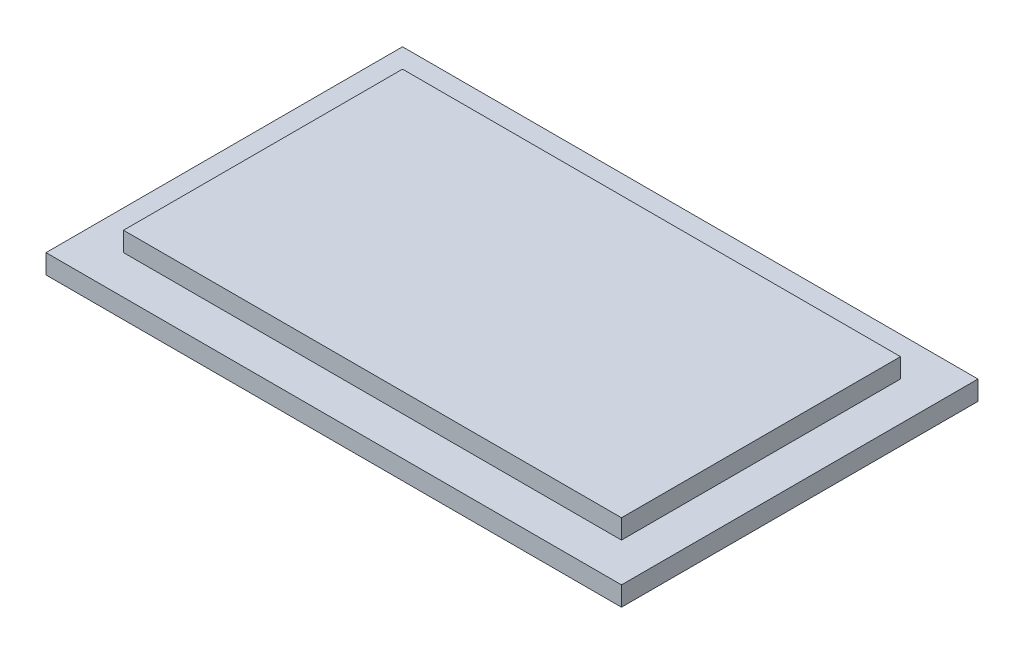
SolidWorks part; units mm, degrees
ref_plane "Front Plane" through (0, 0, 0) normal (0, 0, 1) x (1, 0, 0)
ref_plane "Top Plane" through (0, 0, 0) normal (0, 1, 0) x (1, 0, 0)
ref_plane "Right Plane" through (0, 0, 0) normal (1, 0, 0) x (0, 0, -1)
sketch "Sketch1" plane through (0, 0, 0) normal (0, 1, 0) x (1, 0, 0)
  line L0 (-18.4385, 2.948) -> (-18.4385, -15.452)
  line L1 (-18.4385, -15.452) -> (11.2615, -15.452)
  line L2 (11.2615, -15.452) -> (11.2615, 2.948)
  line L3 (11.2615, 2.948) -> (-18.4385, 2.948)
  line L4 (-16.4385, -13.452) -> (9.2615, -13.452)
  line L5 (9.2615, -13.452) -> (9.2615, 0.948)
  line L6 (9.2615, 0.948) -> (-16.4385, 0.948)
  line L7 (-16.4385, 0.948) -> (-16.4385, -13.452)
extrude "Boss-Extrude1" add sketch "Sketch1" against normal blind 1 contours L0 L1 L2 L3
extrude "Boss-Extrude2" add sketch "Sketch1<3>" along normal blind 1 contours L7 L4 L5 L6
sketch "Sketch1<3>" plane through (0, 0, 0) normal (0, 1, 0) x (1, 0, 0) same geometry as "Sketch1"
